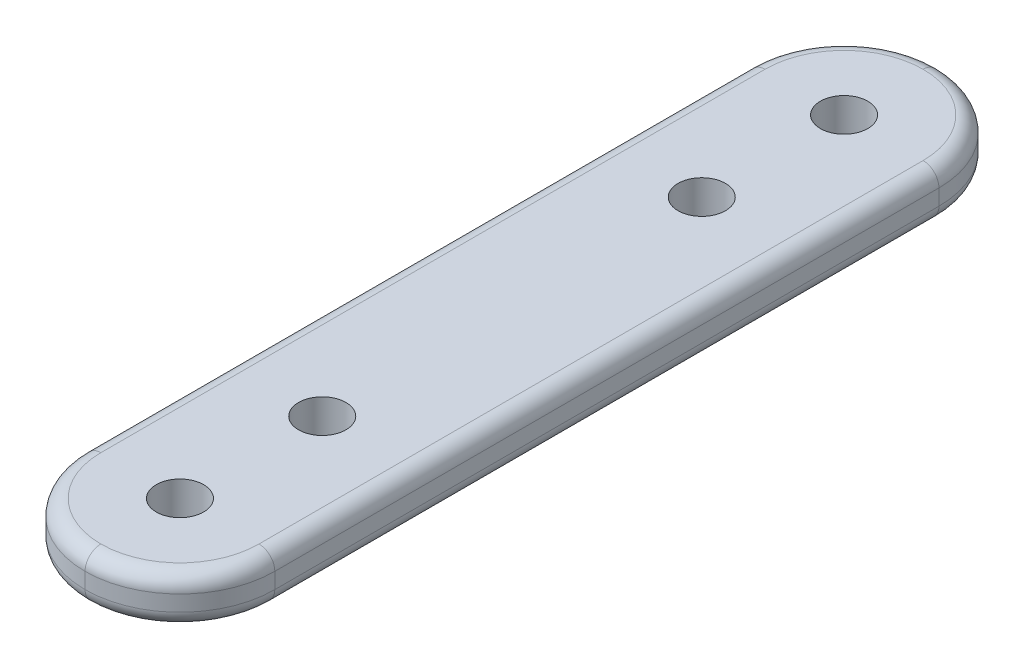
SolidWorks part; units mm, degrees
material "6061 Alloy"
ref_plane "Front Plane" through (0, 0, 0) normal (0, 0, 1) x (1, 0, 0)
ref_plane "Top Plane" through (0, 0, 0) normal (0, 1, 0) x (1, 0, 0)
ref_plane "Right Plane" through (0, 0, 0) normal (1, 0, 0) x (0, 0, -1)
sketch "Sketch1" plane through (0, 0, 0) normal (0, 1, 0) x (1, 0, 0)
  line L0 (0, 57.15) -> (0, -57.15) construction
  line L1 (-12.7, -57.15) -> (12.7, -57.15)
  line L2 (-12.7, -57.15) -> (-12.7, 57.15)
  line L3 (-12.7, 57.15) -> (12.7, 57.15)
  line L4 (12.7, -57.15) -> (12.7, 57.15)
  line L5 (-12.7, -57.15) -> (12.7, 57.15) construction
  line L6 (-12.7, 57.15) -> (12.7, -57.15) construction
  circle A0 centre (0, -44.45) radius 3.175
  circle A1 centre (0, 25.4) radius 3.175
  circle A2 centre (0, 44.45) radius 3.175
  circle A3 centre (0, -25.4) radius 3.175
  point P0 (0, 0)
  dimension "D3" = 6.35
  dimension "D1" = 6.35
  dimension "D8" = 50.8
  dimension "D2" = 25.4
  dimension "D4" = 19.05
  dimension "D5" = 19.05
  dimension "D6" = 12.7
  dimension "D7" = 12.7
extrude "Boss-Extrude1" add sketch "Sketch1" along normal blind 6.35
fillet "Fillet2" radius 12.7 4 edges at (-12.7, 3.175, -57.15) (12.7, 3.175, -57.15) (-12.7, 3.175, 57.15) (12.7, 3.175, 57.15)
fillet "Fillet3" radius 2.1167 12 edges at (8.9803, 6.35, 53.4303) (-8.9803, 6.35, 53.4303) (-12.7, 6.35, 0) (-8.9803, 6.35, -53.4303) (8.9803, 6.35, -53.4303) (8.9803, 0, 53.4303) (-8.9803, 0, 53.4303) (-12.7, 0, 0) (-8.9803, 0, -53.4303) (8.9803, 0, -53.4303) (12.7, 6.35, 0) (12.7, 0, 0)
